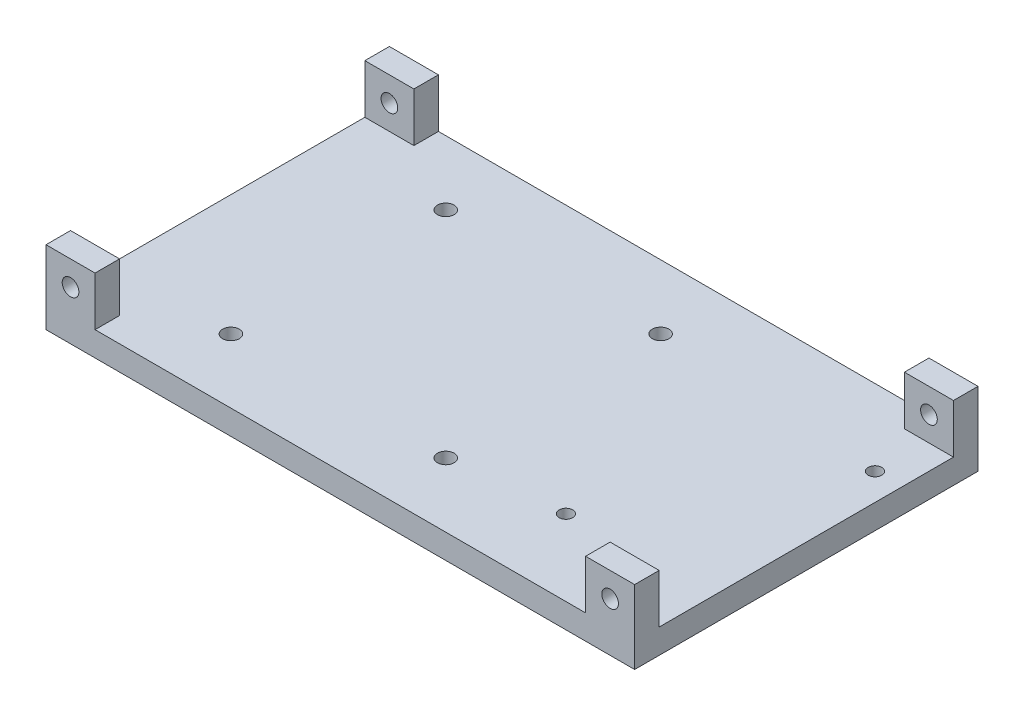
SolidWorks part; units mm, degrees
ref_plane "Front Plane" through (0, 0, 0) normal (0, 0, 1) x (1, 0, 0)
ref_plane "Top Plane" through (0, 0, 0) normal (0, 1, 0) x (1, 0, 0)
ref_plane "Right Plane" through (0, 0, 0) normal (1, 0, 0) x (0, 0, -1)
sketch "Sketch1" plane through (0, 0, 0) normal (0, 1, 0) x (1, 0, 0)
  line L1 (0, 0) -> (-120, 0)
  line L2 (0, 0) -> (0, 70)
  line L3 (0, 70) -> (-120, 70)
  line L4 (-120, 0) -> (-120, 70)
  dimension "D1" = 120
  dimension "D2" = 70
extrude "Boss-Extrude2" add sketch "Sketch1" along normal blind 5
sketch "Sketch2" plane through (0, 5, 0) normal (0, 1, 0) x (1, 0, 0)
  line L1 (-120, 0) -> (-110, 0)
  line L2 (-120, 0) -> (-120, 5)
  line L3 (-120, 5) -> (-110, 5)
  line L4 (-110, 0) -> (-110, 5)
  line L5 (-120, 70) -> (-110, 70)
  line L6 (-120, 70) -> (-120, 65)
  line L7 (-120, 65) -> (-110, 65)
  line L8 (-110, 70) -> (-110, 65)
  line L9 (0, 0) -> (-10, 0)
  line L10 (0, 0) -> (0, 5)
  line L11 (0, 5) -> (-10, 5)
  line L12 (-10, 0) -> (-10, 5)
  line L13 (0, 70) -> (-10, 70)
  line L14 (0, 70) -> (0, 65)
  line L15 (0, 65) -> (-10, 65)
  line L16 (-10, 70) -> (-10, 65)
  dimension "D1" = 5
  dimension "D2" = 10
extrude "Boss-Extrude3" add sketch "Sketch2" along normal blind 10
hole_wizard "M3 Clearance Hole1" positions "Sketch4" profile "Sketch3" hole size "M3" standard "ANSI Metric" end condition through all
sketch "Sketch4" plane through (0, 0, 0) normal (0, 0, 1) x (1, 0, 0)
  line L0 (-120, 15) -> (-120, 0) construction
  line L1 (-120, 15) -> (-110, 15) construction
  line L2 (0, 15) -> (0, 0) construction
  point P0 (-115, 10)
  point P2 (-5, 10)
  dimension "D1" = 5
  dimension "D2" = 5
  dimension "D3" = 5
sketch "Sketch3" plane through (-115, 10, 0) normal (1, 0, 0) x (0, -1, 0)
  line L0 (0, 0) -> (0, 70)
  line L1 (0, 70) -> (1.7, 70)
  line L2 (1.7, 70) -> (1.7, 0)
  line L5 (1.7, 0) -> (0, 0)
  line L11 (0, -6.35) -> (0, 107.95) construction
  dimension "Thru Hole Dia." = 3.4
  dimension "Thru Hole Depth" = 70
sketch "Sketch5" plane through (0, 0, 0) normal (0, -1, 0) x (1, 0, 0)
  circle A0 centre (-5.5, -54.5) radius 1.39
  circle A1 centre (-29.5, -15.5) radius 1.39
  circle A2 centre (-5.5, -54.5) radius 1.39 construction
  circle A3 centre (-29.5, -15.5) radius 1.39 construction
extrude "Cut-Extrude1" cut sketch "Sketch5" against normal through all
hole_wizard "M3 Clearance Hole2" positions "Sketch7" profile "Sketch8" hole size "M3" standard "ANSI Metric" end condition through all
sketch "Sketch7" plane through (0, 0, 0) normal (0, -1, 0) x (-1, 0, 0)
  circle A0 centre (95.4, 56.9) radius 1.75 construction
  circle A1 centre (95.4, 13.1) radius 1.75 construction
  circle A2 centre (51.6, 13.1) radius 1.75 construction
  circle A3 centre (51.6, 56.9) radius 1.75 construction
  point P0 (95.4, 13.1)
  point P2 (51.6, 13.1)
  point P4 (51.6, 56.9)
  point P6 (95.4, 56.9)
sketch "Sketch8" plane through (-95.4, 0, -13.1) normal (1, 0, 0) x (0, 0, -1)
  line L0 (0, 0) -> (0, 15)
  line L1 (0, 15) -> (1.7, 15)
  line L2 (1.7, 15) -> (1.7, 0)
  line L5 (1.7, 0) -> (0, 0)
  line L11 (0, -6.35) -> (0, 107.95) construction
  dimension "Thru Hole Dia." = 3.4
  dimension "Thru Hole Depth" = 15
